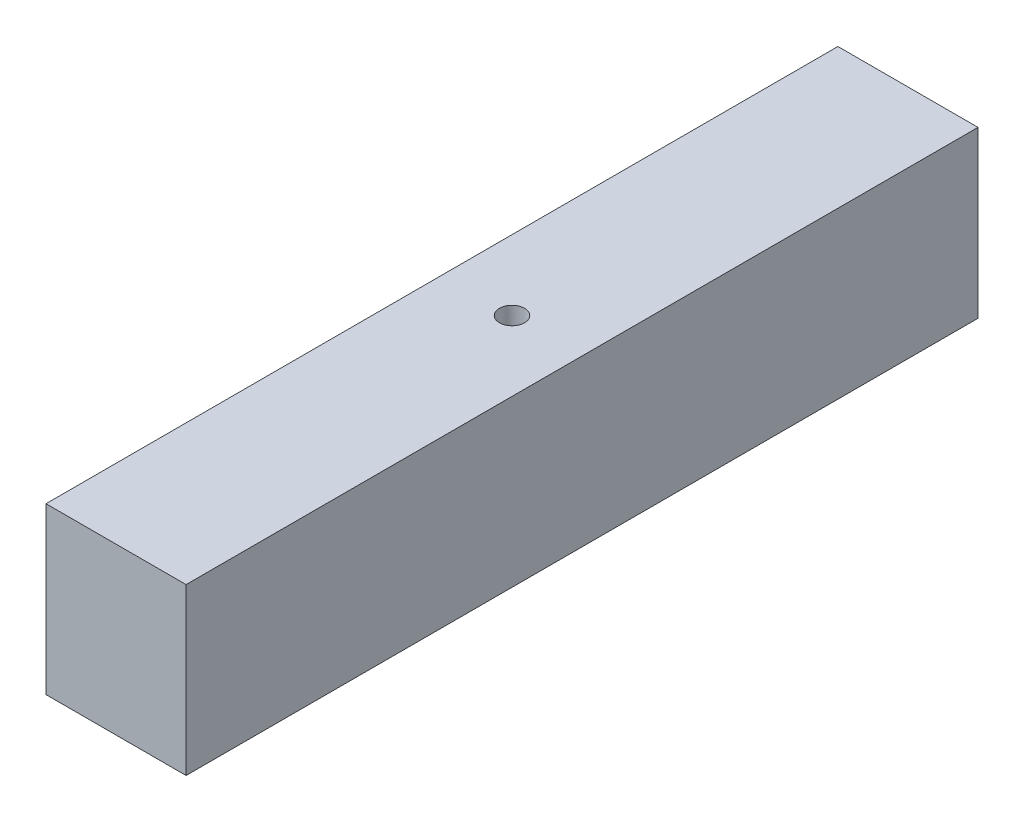
SolidWorks part; units mm, degrees
material "Pine"
ref_plane "Front Plane" through (0, 0, 0) normal (0, 0, 1) x (1, 0, 0)
ref_plane "Top Plane" through (0, 0, 0) normal (0, 1, 0) x (1, 0, 0)
ref_plane "Right Plane" through (0, 0, 0) normal (1, 0, 0) x (0, 0, -1)
sketch "Sketch1" plane through (0, 0, 0) normal (0, 0, 1) x (1, 0, 0)
  line L1 (0, 0) -> (17.69, 0)
  line L2 (0, 0) -> (0, 20.88)
  line L3 (0, 20.88) -> (17.69, 20.88)
  line L4 (17.69, 0) -> (17.69, 20.88)
  dimension "D1" = 17.69
  dimension "D2" = 20.88
extrude "Boss-Extrude1" add sketch "Sketch1" along normal blind 100
sketch "Sketch2" plane through (0, 20.88, 0) normal (0, 1, 0) x (1, 0, 0)
  line L0 (17.69, 0) -> (0, 0) construction
  line L1 (0, -100) -> (0, 0) construction
  circle A0 centre (8.845, -50) radius 1.5875
  point P0 (8.845, 0)
  point P1 (0, -50)
  point P4 (8.845, -50)
  dimension "D1" = 3.175
extrude "Cut-Extrude1" cut sketch "Sketch2" against normal blind 106.78
